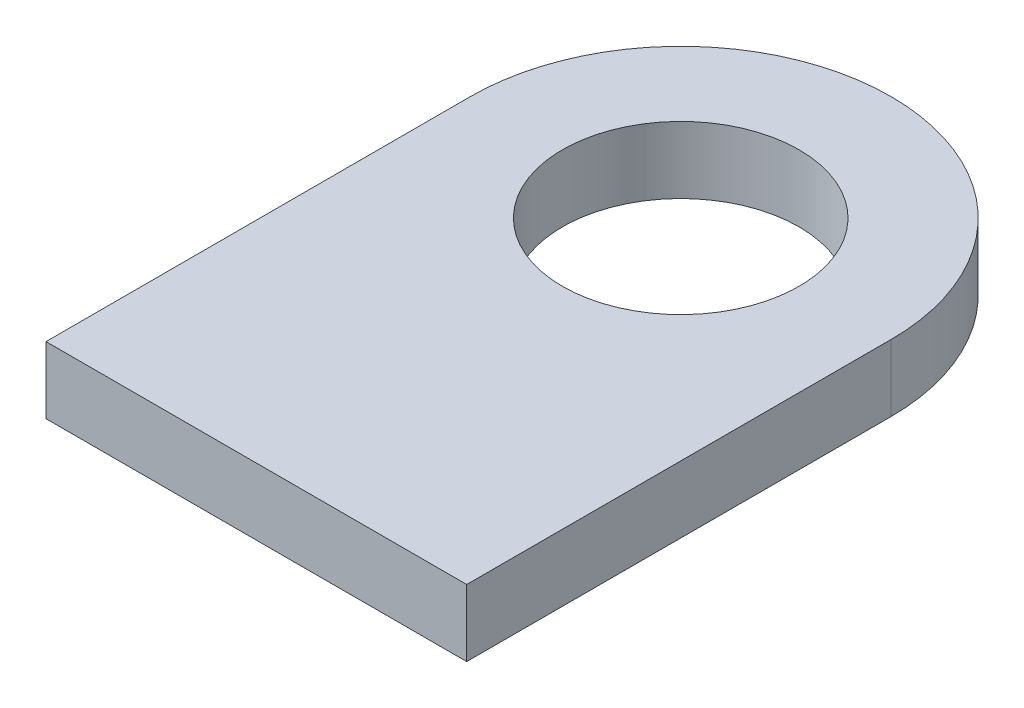
SolidWorks part; units mm, degrees
material "AISI 1020"
ref_plane "Plano frontal" through (0, 0, 0) normal (0, 0, 1) x (1, 0, 0)
ref_plane "Plano superior" through (0, 0, 0) normal (0, 1, 0) x (1, 0, 0)
ref_plane "Plano direito" through (0, 0, 0) normal (1, 0, 0) x (0, 0, -1)
sketch "Esboço1" plane through (0, 0, 0) normal (0, 1, 0) x (1, 0, 0)
  line L0 (0, 0) -> (0, 80.7) construction
  line L1 (-40, 0) -> (40, 0)
  line L2 (40, 0) -> (40, 80.7)
  line L3 (-40, 80.7) -> (-40, 0)
  arc A0 (40, 80.7) -> (-40, 80.7) centre (0, 80.7) ccw
  circle A1 centre (0, 80.7) radius 22.5
  dimension "D3" = 45
  dimension "D1" = 80.7
  dimension "D2" = 80
base flange "Flange-base1" sketch "Esboço1" thickness 12.7 reverse thickness direction no parameters "D1"=0.7366
sketch "Curva-Linhas1" [suppressed] plane through (0, 0, 0) normal (0, 1, 0) x (1, 0, 0)
sketch "Caixa delimitadora1" [suppressed] plane through (0, 0, 0) normal (0, 1, 0) x (1, 0, 0)
sheet metal parameters "Chapa metálica1" thickness 12.7 parameters "D1"=0.7366
flat pattern "Padrão-Plano1" [suppressed]
sketch "Curva-Linhas2" plane through (0, 0, 0) normal (0, 1, 0) x (1, 0, 0)
sketch3d "Caixa delimitadora2" [suppressed]
  line L0 (40, 40, 0) -> (40, -80.7, 0) construction
  line L1 (-40, 40, 0) -> (-40, -80.7, 0) construction
  line L2 (40, 40, 0) -> (-40, 40, 0) construction
  line L3 (40, -80.7, 0) -> (-40, -80.7, 0) construction
